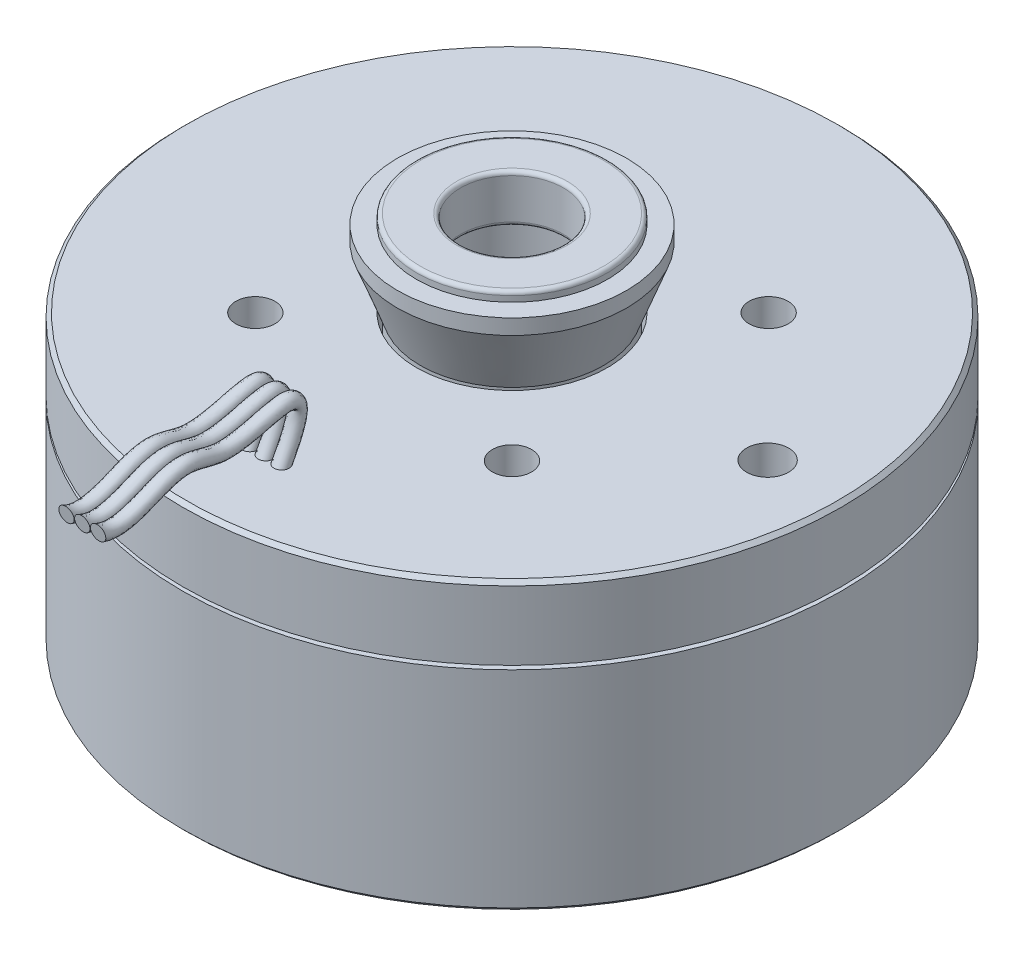
SolidWorks part; units mm, degrees
ref_plane "前视基准面" through (0, 0, 0) normal (0, 0, 1) x (1, 0, 0)
ref_plane "上视基准面" through (0, 0, 0) normal (0, 1, 0) x (1, 0, 0)
ref_plane "右视基准面" through (0, 0, 0) normal (1, 0, 0) x (0, 0, -1)
sketch "草图1" plane through (0, 0, 0) normal (0, 0, 1) x (1, 0, 0)
  line L0 (0, 0) -> (0, 52.1824) construction
  line L1 (-3.25, 0) -> (-3.25, 19)
  line L2 (-3.25, 19) -> (-6, 19)
  line L3 (-6, 19) -> (-6, 15)
  line L4 (-6, 15) -> (-17.25, 15)
  line L5 (-17.25, 15) -> (-17.25, 0)
  line L6 (-17.25, 0) -> (-3.25, 0)
  dimension "D1" = 6.5
  dimension "D2" = 19
  dimension "D3" = 15
  dimension "D4" = 34.5
  dimension "D5" = 12
revolve "旋转1" add sketch "草图1" angle 360 about L0
chamfer "倒角1" distance 0.2 angle 45 2 edges at (0, 0, -17.25) (0, 15, -17.25)
sketch "草图3" plane through (0, 0, 0) normal (0, -1, 0) x (1, 0, 0)
  circle A0 centre (0, 0) radius 17.25 construction
  circle A1 centre (0, 0) radius 17.25
extrude "切除-拉伸2" cut sketch "草图3" against normal blind 0.2 from offset 11 offset against normal yes
hole_wizard "M2.5 螺纹孔1" positions "草图4" profile "草图5" tap size "M2.5" standard "GB"
sketch "草图4" plane through (0, 15, 0) normal (0, 1, 0) x (1, 0, 0)
  line L0 (-6.7175, 6.7175) -> (6.7175, 6.7175) construction
  line L1 (6.7175, 6.7175) -> (6.7175, -6.7175) construction
  line L2 (6.7175, -6.7175) -> (-6.7175, -6.7175) construction
  line L3 (-6.7175, -6.7175) -> (-6.7175, 6.7175) construction
  line L4 (-6.7175, 6.7175) -> (6.7175, -6.7175) construction
  point P0 (-6.7175, 6.7175)
  point P2 (6.7175, 6.7175)
  point P4 (6.7175, -6.7175)
  point P6 (-6.7175, -6.7175)
  dimension "D1" = 19
sketch "草图5" plane through (-6.7175, 15, -6.7175) normal (1, 0, 0) x (0, 0, 1)
  line L0 (0, 0) -> (0, 7.0159)
  line L1 (0, 7.0159) -> (1.025, 6.4)
  line L2 (1.025, 6.4) -> (1.025, 0)
  line L5 (1.025, 0) -> (0, 0)
  line L10 (0, 7.0159) -> (-1.025, 6.4) construction
  line L11 (0, -6.35) -> (0, 107.95) construction
  dimension "螺纹孔钻头直径" = 2.05
  dimension "螺纹孔钻头深度" = 6.4
  dimension "导头角度" = 118
cosmetic thread "孔螺蚊线1" parameters "D1"=5, "D2"=2.5
cosmetic thread "孔螺蚊线2" parameters "D1"=5, "D2"=2.5
cosmetic thread "孔螺蚊线3" parameters "D1"=5, "D2"=2.5
cosmetic thread "孔螺蚊线4" parameters "D1"=5, "D2"=2.5
chamfer "倒角2" distance 0.1 angle 45 1 edges at (0, 0, -3.25)
hole_wizard "M2.5 螺纹孔2" positions "草图8" profile "草图9" tap size "M2.5" standard "GB"
sketch "草图8" plane through (0, 0, 0) normal (0, -1, 0) x (-1, 0, 0)
  line L0 (0, 0) -> (5.6569, -5.6569) construction
  line L2 (0, 0) -> (0, -10.754) construction
  point P0 (5.6569, -5.6569)
  dimension "D1" = 45
  dimension "D2" = 8
sketch "草图9" plane through (-5.6569, 0, 5.6569) normal (1, 0, 0) x (0, 0, -1)
  line L0 (0, 0) -> (0, 7.0159)
  line L1 (0, 7.0159) -> (1.025, 6.4)
  line L2 (1.025, 6.4) -> (1.025, 0)
  line L5 (1.025, 0) -> (0, 0)
  line L10 (0, 7.0159) -> (-1.025, 6.4) construction
  line L11 (0, -6.35) -> (0, 107.95) construction
  dimension "螺纹孔钻头直径" = 2.05
  dimension "螺纹孔钻头深度" = 6.4
  dimension "导头角度" = 118
cosmetic thread "孔螺蚊线5" parameters "D1"=5, "D2"=2.5
pattern_circular "阵列(圆周)1" count 4 over 360 about axis through (0, 0, 0) along (0, -1, 0) of "M2.5 螺纹孔2" reverse direction yes
cosmetic thread "孔螺蚊线6" parameters "D1"=5, "D2"=2.5
cosmetic thread "孔螺蚊线7" parameters "D1"=5, "D2"=2.5
cosmetic thread "孔螺蚊线8" parameters "D1"=5, "D2"=2.5
sketch "草图10" plane through (0, 0, 0) normal (1, 0, 0) x (0, 0, -1)
  line L0 (17.05, 15) -> (-17.05, 15) construction
  spline S0 degree 3 poles (-13.0066, 15) (-10.6736, 19.2627) (-14.8128, 16.1539) (-18.7748, 18.0594) (-20.9025, 15.934) (-22.4807, 16.5619) knots 0 0 0 0 0.483563 0.635945 1 1 1 1
sketch "草图11" plane through (0, 15, 0) normal (0, 1, 0) x (1, 0, 0)
  line L0 (0, -22.4807) -> (0, -12.1841) construction
  circle A0 centre (0, -12.8864) radius 0.4
  circle A1 centre (-0.8279, -12.8864) radius 0.4
  circle A2 centre (0.8274, -12.8864) radius 0.4
  dimension "D1" = 0.8
sweep "扫描1" add profiles "草图11" path "草图10"
hole_wizard "Ø2.2 (2.2) 直径孔2" positions "草图12" profile "草图13" hole size "Ø2.2" standard "GB"
sketch "草图12" plane through (0, 15, 0) normal (0, 1, 0) x (1, 0, 0)
  point P0 (13.3813, 0)
sketch "草图13" plane through (13.3813, 15, 0) normal (1, 0, 0) x (0, 0, 1)
  line L0 (0, 0) -> (0, 4.6609)
  line L1 (0, 4.6609) -> (1.1, 4)
  line L2 (1.1, 4) -> (1.1, 0)
  line L5 (1.1, 0) -> (0, 0)
  line L10 (0, 4.6609) -> (-1.1, 4) construction
  line L11 (0, -6.35) -> (0, 107.95) construction
  dimension "孔直径" = 2.2
  dimension "孔深度" = 4
  dimension "导头角度" = 118
hole_wizard "Ø2.2 (2.2) 直径孔1" positions "草图16" profile "草图17" hole size "Ø2.2" standard "GB"
sketch "草图16" plane through (0, 0, 0) normal (0, -1, 0) x (-1, 0, 0)
  line L0 (5.6569, 5.6569) -> (-5.6569, -5.6569) construction
  line L1 (-5.6569, -5.6569) -> (-7.7782, -7.7782) construction
  point P0 (-7.7782, -7.7782)
  dimension "D1" = 3
sketch "草图17" plane through (7.7782, 0, 7.7782) normal (1, 0, 0) x (0, 0, -1)
  line L0 (0, 0) -> (0, 4.6609)
  line L1 (0, 4.6609) -> (1.1, 4)
  line L2 (1.1, 4) -> (1.1, 0)
  line L5 (1.1, 0) -> (0, 0)
  line L10 (0, 4.6609) -> (-1.1, 4) construction
  line L11 (0, -6.35) -> (0, 107.95) construction
  dimension "孔直径" = 2.2
  dimension "孔深度" = 4
  dimension "导头角度" = 118
sketch "草图18" plane through (0, 0, 0) normal (0, 0, 1) x (1, 0, 0)
  line L0 (-6, 18.2) -> (-4.8, 15)
  line L1 (-6, 19) -> (-6, 15) construction
  line L2 (17.05, 15) -> (-17.05, 15) construction
  line L3 (-4.8, 15) -> (-6, 15)
  line L4 (-6, 15) -> (-6, 18.2)
  line L5 (0, 0) -> (0, 28.0429) construction
  dimension "D1" = 1.2
  dimension "D2" = 3.2
revolve "切除-旋转1" cut sketch "草图18" angle 360 about L5
sketch "草图20" plane through (0, 15, 0) normal (0, 1, 0) x (1, 0, 0)
  circle A0 centre (0, 0) radius 5
  dimension "D1" = 10
extrude "切除-拉伸4" cut sketch "草图20" against normal up to surface (3.8 mm away) up to face at (13.3813, 11.2, -1.1)
sketch "草图21" plane through (0, 15, 0) normal (0, 1, 0) x (1, 0, 0)
  circle A0 centre (0, 0) radius 4.8
  circle A1 centre (0, 0) radius 4.8 construction
  circle A2 centre (0, 0) radius 3.25 construction
  circle A3 centre (0, 0) radius 3.25
extrude "凸台-拉伸1" add sketch "草图21" against normal up to surface (15 mm away) and the other way blind 1 up to face at (7.7782, 0, 6.6782)
sketch "草图22" plane through (0, 19, 0) normal (0, 1, 0) x (1, 0, 0)
  circle A0 centre (0, 0) radius 5
  dimension "D1" = 10
extrude "切除-拉伸5" cut sketch "草图22" against normal blind 2
sketch "草图23" plane through (0, 17, 0) normal (0, 1, 0) x (1, 0, 0)
  circle A0 centre (0, 0) radius 5
  circle A1 centre (0, 0) radius 2.7
  dimension "D1" = 10
  dimension "D2" = 5.4
extrude "凸台-拉伸2" add sketch "草图23" along normal blind 2.5 separate body
fillet "圆角1" radius 0.2 3 edges at (0, 19.5, 5) (0, 17, 2.7) (0, 19.5, 2.7)
